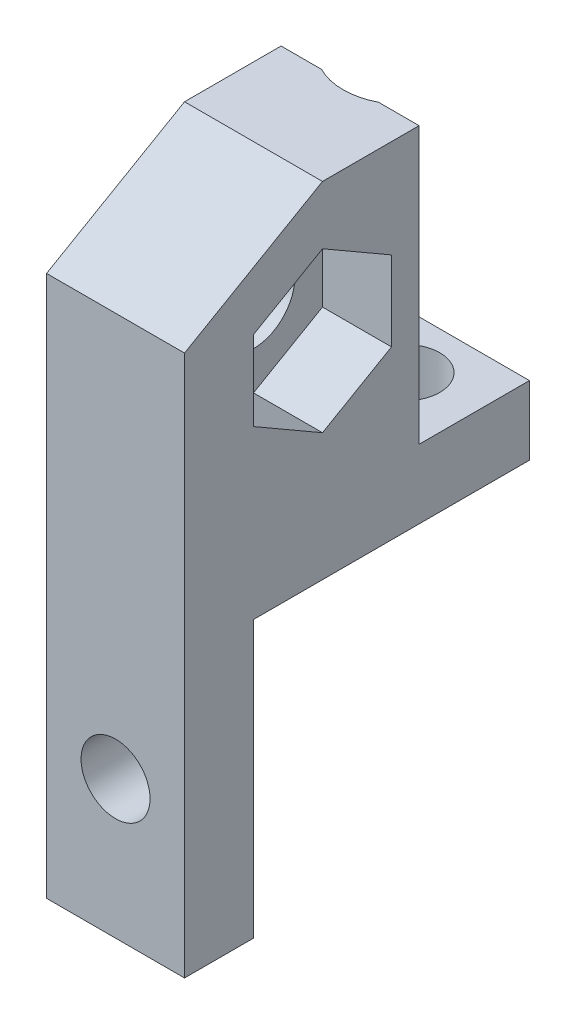
SolidWorks part; units mm, degrees
ref_plane "정면" through (0, 0, 0) normal (0, 0, 1) x (1, 0, 0)
ref_plane "윗면" through (0, 0, 0) normal (0, 1, 0) x (1, 0, 0)
ref_plane "우측면" through (0, 0, 0) normal (1, 0, 0) x (0, 0, -1)
sketch "스케치1" plane through (0, 0, 0) normal (1, 0, 0) x (0, 0, -1)
  line L0 (0, 0) -> (0, -20)
  line L1 (0, -20) -> (-5, -20)
  line L2 (-5, -20) -> (-5, 25)
  line L3 (-5, 25) -> (20, 25)
  line L4 (20, 25) -> (20, 0)
  line L5 (20, 0) -> (0, 0)
  line L7 (5, 20.7735) -> (0, 17.8868)
  line L8 (0, 17.8868) -> (0, 12.1132)
  line L9 (0, 12.1132) -> (5, 9.2265)
  line L10 (5, 9.2265) -> (10, 12.1132)
  line L11 (10, 12.1132) -> (10, 17.8868)
  line L12 (10, 17.8868) -> (5, 20.7735)
  circle A0 centre (5, 15) radius 5 construction
  circle A1 centre (5, 15) radius 3
  dimension "D3" = 6
  dimension "D1" = 20
  dimension "D2" = 10
  dimension "D4" = 15
  dimension "D5" = 5
  dimension "D6" = 15
  dimension "D7" = 25
extrude "보스-돌출1" add sketch "스케치1" along normal blind 5 contours L5 L4 L3 L2 L1 L0 L12 L11 L10 L9 L8 L7 | L11 L12 L7 L8 L9 L10 A1 region at (0, 8.6364, -6.2727) region at (0, 19.1978, -7.4236)
extrude "보스-돌출2" add sketch "스케치1<3>" along normal blind 5 from surface contours L5 L4 L3 L2 L1 L0 L12 L11 L10 L9 L8 L7 region at (0, 8.6364, -6.2727) starting at face at (5, 1.6667, -5)
sketch "스케치1<3>" plane through (0, 0, 0) normal (1, 0, 0) x (0, 0, -1) same geometry as "스케치1"
sketch "스케치3" plane through (0, 0, 5) normal (0, 0, 1) x (1, 0, 0)
  line L0 (5, 25) -> (5, -20) construction
  line L1 (10, 25) -> (0, 25) construction
  line L2 (10, -20) -> (0, -20) construction
  circle A0 centre (5, -10) radius 2.5
  dimension "D1" = 5
  dimension "D2" = 10
extrude "컷-돌출1" cut sketch "스케치3" against normal through all
chamfer "모따기1" distance 10 angle 30 1 edges at (5, 25, 5) first distance on face at (5, 25, -7.5)
sketch "스케치4" plane through (10, 0, 0) normal (1, 0, 0) x (0, 0, -1)
  line L0 (20, 25) -> (5, 25) construction
  line L1 (12, 25) -> (20, 25)
  line L2 (12, 25) -> (12, 5)
  line L3 (12, 5) -> (20, 5)
  line L4 (20, 25) -> (20, 5)
  line L5 (20, 0) -> (20, 25) construction
  line L6 (0, 0) -> (20, 0) construction
  dimension "D1" = 5
  dimension "D2" = 8
extrude "컷-돌출2" cut sketch "스케치4" against normal through all
sketch "스케치5" plane through (0, 5, 0) normal (0, 1, 0) x (1, 0, 0)
  line L0 (5, 12) -> (5, 20) construction
  line L4 (10, 12) -> (10, 20)
  line L5 (10, 20) -> (0, 20)
  line L6 (0, 20) -> (0, 12)
  line L7 (0, 12) -> (10, 12)
  line L8 (10, 12) -> (10, 20)
  line L9 (10, 20) -> (0, 20)
  line L10 (0, 20) -> (0, 12)
  line L11 (0, 12) -> (10, 12)
  circle A0 centre (5, 16) radius 4.5
  circle A1 centre (5, 16) radius 2.5
  dimension "D2" = 9
  dimension "D3" = 5
  dimension "D1" = 0
extrude "컷-돌출3" cut sketch "스케치5" along normal through all contours A0
extrude "컷-돌출4" cut sketch "스케치5<3>" against normal through all contours A1 L0 | L0 A1 region at (3.939, 5, -16) region at (6.061, 5, -16)
sketch "스케치5<3>" plane through (0, 5, 0) normal (0, 1, 0) x (1, 0, 0) same geometry as "스케치5"
